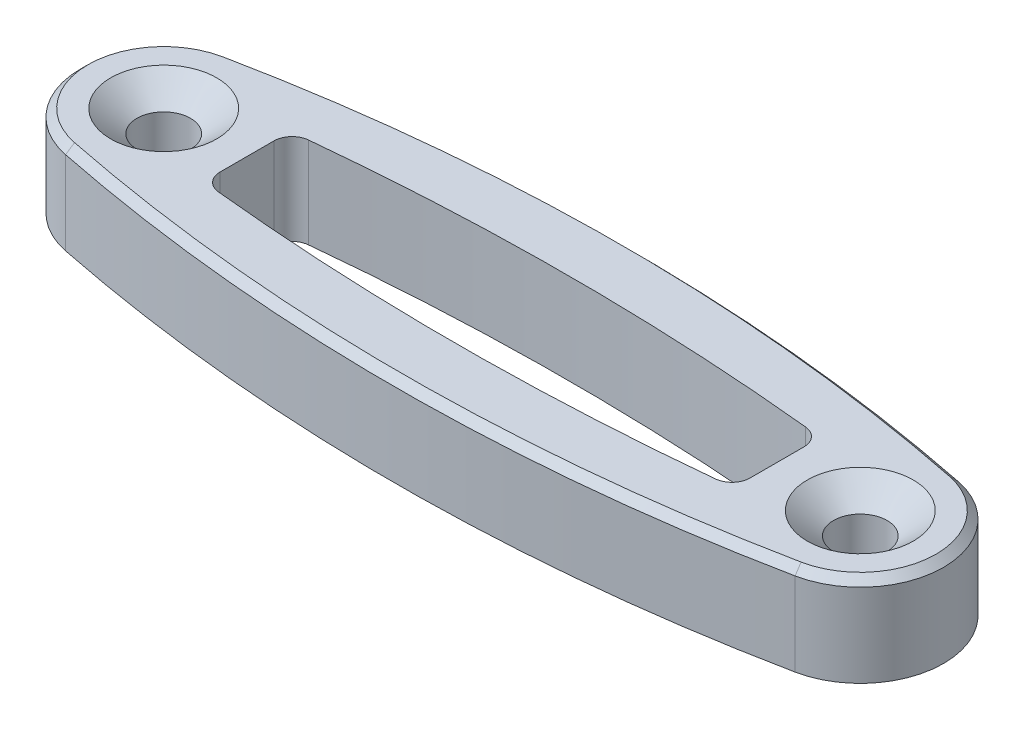
SolidWorks part; units mm, degrees
ref_plane "Front Plane" through (0, 0, 0) normal (0, 0, 1) x (1, 0, 0)
ref_plane "Top Plane" through (0, 0, 0) normal (0, 1, 0) x (1, 0, 0)
ref_plane "Right Plane" through (0, 0, 0) normal (1, 0, 0) x (0, 0, -1)
sketch "Sketch1" plane through (0, 0, 0) normal (0, 1, 0) x (1, 0, 0)
  line L1 (0, 4.826) -> (0, -4.826) construction
  line L2 (21.717, 2.2586) -> (21.717, -2.2586) construction
  line L3 (22.225, 2.2586) -> (22.225, -2.2586)
  line L4 (0, 9.906) -> (0, 4.826)
  line L5 (0, -9.906) -> (0, -4.826)
  arc A8 (0, 4.318) -> (20.8032, 3.2694) centre (0, -202.565) cw construction
  arc A9 (0, -4.318) -> (20.8032, -3.2694) centre (0, 202.565) ccw construction
  arc A10 (30.5932, -6.8467) -> (30.5932, 6.8467) centre (29.21, 0) ccw
  arc A11 (21.717, 2.2586) -> (20.8032, 3.2694) centre (20.701, 2.2586) ccw construction
  arc A12 (21.717, -2.2586) -> (20.8032, -3.2694) centre (20.701, -2.2586) cw construction
  arc A13 (0, 4.826) -> (20.8542, 3.7748) centre (0, -202.565) cw
  arc A14 (22.225, 2.2586) -> (20.8542, 3.7748) centre (20.701, 2.2586) ccw
  arc A15 (22.225, -2.2586) -> (20.8542, -3.7748) centre (20.701, -2.2586) cw
  arc A16 (0, -4.826) -> (20.8542, -3.7748) centre (0, 202.565) ccw
  arc A17 (0, 4.318) -> (20.8032, 3.2694) centre (0, -202.565) cw construction
  arc A18 (0, 9.906) -> (30.5932, 6.8467) centre (0, -144.5895) cw
  arc A19 (0, -9.906) -> (30.5932, -6.8467) centre (0, 144.5895) ccw
  point P10 (21.717, 3.175)
  point P16 (21.717, 0)
  point P17 (21.717, -3.175)
  point P32 (0, 0)
  dimension "D1" = 13.97
  dimension "D2" = 6.35
  dimension "D3" = 8.636
  dimension "D5" = 1.016
  dimension "D4" = 21.717
  dimension "D7" = 5.08
  dimension "D6" = 0.508
extrude "Boss-Extrude1" add sketch "Sketch1" along normal blind 7.62
hole_wizard "CSK for #8 Flat Head Machine Screw (100)1" positions "Sketch2" profile "Sketch3" countersink size "#8" standard "ANSI Inch" end condition through all
sketch "Sketch2" plane through (0, 7.62, 0) normal (0, 1, 0) x (1, 0, 0)
  point P7 (29.21, 0)
sketch "Sketch3" plane through (29.21, 7.62, 0) normal (1, 0, 0) x (0, 0, 1)
  line L0 (0, 0) -> (0, 7.62)
  line L1 (0, 7.62) -> (2.2479, 7.62)
  line L2 (2.2479, 7.62) -> (2.2479, 1.8436)
  line L3 (2.2479, 1.8436) -> (4.445, 0)
  line L5 (4.445, 0) -> (0, 0)
  line L6 (-2.2479, 1.8436) -> (-4.445, 0) construction
  line L11 (0, -6.35) -> (0, 107.95) construction
  dimension "Thru Hole Dia." = 4.4958
  dimension "Thru Hole Depth" = 7.62
  dimension "Near C'Sink Dia." = 8.89
  dimension "Near C'Sink Angle" = 100
mirror "Mirror1" about plane through (0, 0, 0) normal (1, 0, 0) of bodies 106
chamfer "Chamfer1" distance 0.635 angle 45 4 edges at (0, 7.62, -9.906) (-36.195, 7.62, 0) (36.195, 7.62, 0) (0, 7.62, 9.906)
